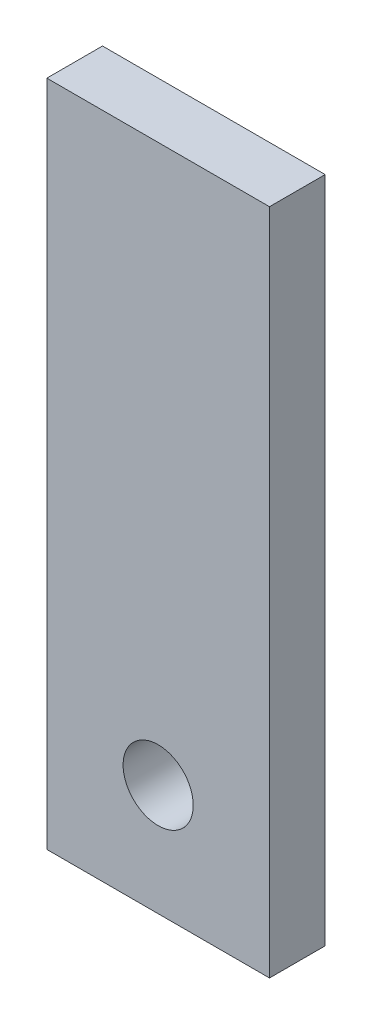
SolidWorks part; units mm, degrees
material "1060 Alloy"
ref_plane "Front Plane" through (0, 0, 0) normal (0, 0, 1) x (1, 0, 0)
ref_plane "Top Plane" through (0, 0, 0) normal (0, 1, 0) x (1, 0, 0)
ref_plane "Right Plane" through (0, 0, 0) normal (1, 0, 0) x (0, 0, -1)
sketch "Sketch1" plane through (0, 0, 0) normal (0, 0, 1) x (1, 0, 0)
  line L0 (55, 0) -> (-55, 0) construction
  line L1 (-12.7, -38.1) -> (12.7, -38.1)
  line L2 (-12.7, -38.1) -> (-12.7, 38.1)
  line L3 (-12.7, 38.1) -> (12.7, 38.1)
  line L4 (12.7, -38.1) -> (12.7, 38.1)
  line L5 (-12.7, -38.1) -> (12.7, 38.1) construction
  line L6 (-12.7, 38.1) -> (12.7, -38.1) construction
  line L7 (-12.7, 38.1) -> (12.7, 38.1)
  line L8 (-12.7, 38.1) -> (-12.7, 44.45)
  line L9 (-12.7, 44.45) -> (12.7, 44.45)
  line L10 (12.7, 38.1) -> (12.7, 44.45)
  line L11 (-12.7, -44.45) -> (12.7, -44.45)
  line L12 (12.7, -38.1) -> (12.7, -44.45)
  line L13 (-12.7, -38.1) -> (12.7, -38.1)
  line L14 (-12.7, -38.1) -> (-12.7, -44.45)
  point P0 (0, 0)
  point P10 (0, 44.45)
  point P11 (0, 38.1)
  point P18 (0, -38.1)
  point P19 (0, -44.45)
  dimension "D1" = 25.4
  dimension "D2" = 76.2
  dimension "D3" = 25.4
  dimension "D4" = 6.35
extrude "Boss-Extrude1" add sketch "Sketch1" along normal blind 6.35 contours L1 L4 L3 L2 region at (0, 0, 0)
sketch "Sketch2" plane through (0, 0, 6.35) normal (0, 0, 1) x (1, 0, 0)
  line L8 (-12.7, -38.1) -> (12.7, -38.1) construction
  circle A1 centre (0, -25.4) radius 4
  dimension "D2" = 12.7
  dimension "D1" = 8
extrude "Cut-Extrude1" cut sketch "Sketch2" against normal through all
